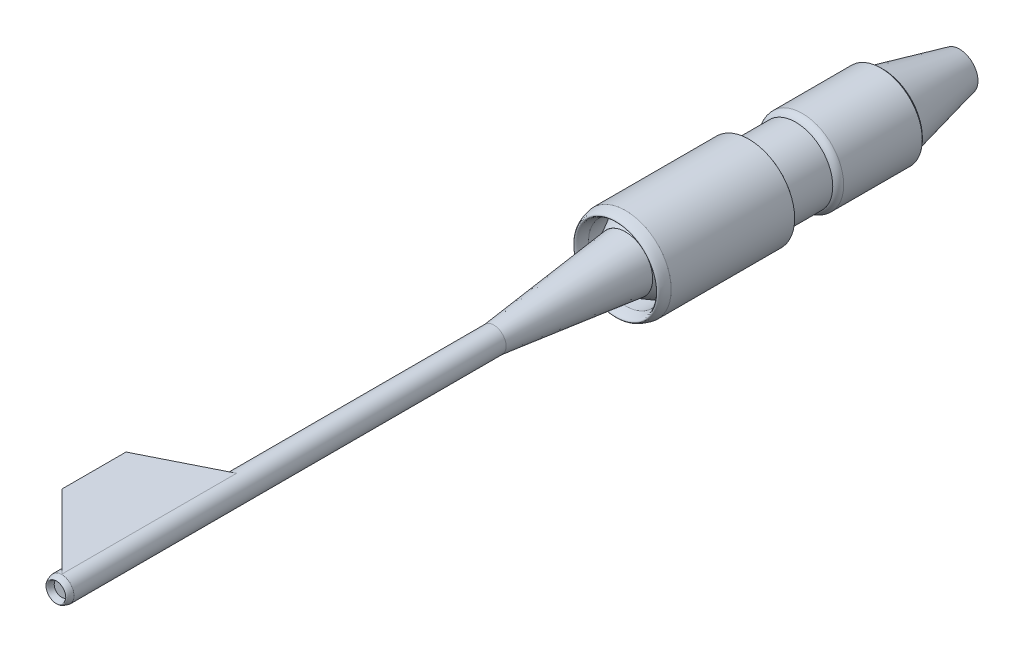
SolidWorks part; units mm, degrees
ref_plane "Front Plane" through (0, 0, 0) normal (0, 0, 1) x (1, 0, 0)
ref_plane "Top Plane" through (0, 0, 0) normal (0, 1, 0) x (1, 0, 0)
ref_plane "Right Plane" through (0, 0, 0) normal (1, 0, 0) x (0, 0, -1)
sketch "Sketch1" plane through (0, 0, 0) normal (0, 0, 1) x (1, 0, 0)
  circle A0 centre (0, 0) radius 416.25
  circle A1 centre (0, 0) radius 337.5
extrude "Boss-Extrude1" add sketch "Sketch1" against normal blind 1125
sketch "Sketch2" plane through (0, 0, 0) normal (1, 0, 0) x (0, 0, -1)
  line L0 (0, 416.25) -> (0, 337.5) construction
  line L1 (0, 337.5) -> (0, 376.875) construction
  line L2 (0, 376.875) -> (-90, 376.875) construction
  line L3 (0, 416.25) -> (0, 337.5)
  line L4 (0, 0) -> (98.8797, 0) construction
  spline S0 degree 2 poles (0, 337.5) (-180, 376.875) (0, 416.25) knots 0 0 0 1 1 1
revolve "Revolve1" add sketch "Sketch2" angle 360 about L4
ref_plane "Plane1" through (0, 0, 0) normal (0, 0, 1) x (1, 0, 0)
sketch "Sketch3" plane through (0, 0, 0) normal (0, 0, 1) x (1, 0, 0)
  circle A0 centre (0, 0) radius 247.5
sketch "Sketch4" plane through (0, 0, 0) normal (0, 1, 0) x (1, 0, 0)
  line L0 (0, 0) -> (0, -1200)
  line L1 (0, -1200) -> (112.5, -1200)
  line L2 (0, 0) -> (247.5, 0)
  line L3 (-247.5, 0) -> (247.5, 0) construction
  line L4 (-457.875, 0) -> (457.875, 0) construction
  line L5 (247.5, 0) -> (112.5, -1200)
revolve "Revolve2" add sketch "Sketch4" angle 360 about L0
sketch "Sketch5" plane through (0, 0, 1200) normal (0, 0, 1) x (1, 0, 0)
  circle A0 centre (0, 0) radius 112.5
extrude "Boss-Extrude2" add sketch "Sketch5" along normal blind 3937.5
sketch "Sketch14" plane through (0, 0, 0) normal (1, 0, 0) x (0, 0, -1)
  line L0 (-5137.5, 112.5) -> (-5137.5, 67.5)
  line L1 (-5137.5, 112.5) -> (-5137.5, -112.5) construction
  line L2 (-5137.5, 67.5) -> (-5137.5, 90)
  line L3 (-5137.5, 90) -> (-5187.5, 90) construction
  line L4 (-5137.5, 0) -> (-5198.2274, 0) construction
  line L5 (-5137.5, 112.5) -> (-5137.5, -112.5) construction
  spline S0 degree 2 poles (-5137.5, 67.5) (-5237.5, 90) (-5137.5, 112.5) knots 0 0 0 1 1 1
  dimension "D1" = 50
  dimension "D2" = 67.5
  dimension "D3" = 90
revolve "Revolve4" add sketch "Sketch14" angle 360 about L4 region at (0, 90, 5157.5)
sketch "Sketch15" plane through (0, 0, -1125) normal (0, 0, -1) x (-1, 0, 0)
  circle A0 centre (0, 0) radius 337.5
extrude "Boss-Extrude5" add sketch "Sketch15" along normal blind 486 separate body
sketch "Sketch16" plane through (0, 0, -1611) normal (0, 0, -1) x (-1, 0, 0)
  line L0 (0, 337.5) -> (0, 416.25) construction
  line L1 (0, 376.875) -> (79.8334, 376.875) construction
  circle A0 centre (0, 0) radius 337.5 construction
  circle A1 centre (0, 0) radius 337.5 construction
  circle A2 centre (0, 0) radius 416.25 construction
  circle A4 centre (0, 0) radius 376.875
extrude "Boss-Extrude6" add sketch "Sketch16" along normal blind 716
sketch "Sketch17" plane through (0, 0, 0) normal (1, 0, 0) x (0, 0, -1)
  line L0 (2327, 0) -> (3043, 0)
  line L1 (2327, -376.875) -> (2327, 376.875) construction
  line L2 (3043, 0) -> (3043, 168.75)
  line L3 (1611, 337.5) -> (2327, 337.5) construction
  line L4 (2327, 0) -> (2327, 337.5)
  line L5 (2327, 337.5) -> (3043, 168.75)
revolve "Revolve5" add sketch "Sketch17" angle 360 about L0
sketch "Sketch18" plane through (0, 0, 0) normal (1, 0, 0) x (0, 0, -1)
  line L0 (0, 247.5) -> (306.6324, 416.25)
  line L1 (1125, 416.25) -> (0, 416.25) construction
  line L2 (0, 247.5) -> (306.6324, 247.5)
  line L3 (306.6324, 247.5) -> (306.6324, 416.25)
  line L4 (0, 0) -> (306.6324, 0) construction
revolve "Revolve6" add sketch "Sketch18" angle 360 about L4
sketch "Sketch19" plane through (0, 0, 0) normal (1, 0, 0) x (0, 0, -1)
  line L1 (1611, 337.5) -> (1611, -337.5) construction
  line L2 (1611, 0) -> (1611, 337.5) construction
  line L3 (1611, 337.5) -> (1551, 337.5)
  line L4 (1611, 0) -> (1571, 0) construction
  line L5 (1611, 337.5) -> (1125, 337.5) construction
  line L6 (1611, 337.5) -> (1611, 376.875)
  line L7 (1611, 376.875) -> (1611, -376.875) construction
  arc A0 (1551, 337.5) -> (1611, 376.875) centre (1614.9642, 305.4325) cw
revolve "Revolve9" add sketch "Sketch19" angle 360 about L4
sketch "Sketch20" plane through (0, 0, 0) normal (1, 0, 0) x (0, 0, -1)
  line L0 (1125, 337.5) -> (1125, 416.25)
  line L1 (1125, 337.5) -> (1155, 337.5)
  line L2 (1551, 337.5) -> (1125, 337.5) construction
  line L3 (1125, 0) -> (1175, 0) construction
  line L4 (1125, -416.25) -> (1125, 416.25) construction
  conic Q0 (1155, 337.5) -> (1125, 416.25) control (1155, 382.5893) rho 0.44632
revolve "Revolve11" add sketch "Sketch20" angle 360 about L3
sketch "Sketch21" plane through (0, 0, 0) normal (1, 0, 0) x (0, 0, -1)
  line L0 (2327, 337.5) -> (2327, 376.875)
  line L1 (2327, 0) -> (2377, 0) construction
  line L2 (2327, -376.875) -> (2327, 376.875) construction
  line L3 (2327, 337.5) -> (2356.2, 330.618)
  line L4 (3043, 168.75) -> (2327, 337.5) construction
  conic Q0 (2327, 376.875) -> (2356.2, 330.618) control (2356.2, 357.1875) rho 0.453502
revolve "Revolve12" add sketch "Sketch21" angle 360 about L1
sketch3d "3DSketch1"
  line L0 (1.7689, 112.4861, 5137.5) -> (-673.2311, 112.4861, 5137.5) construction
  circle A0 centre (0, 0, 5137.5) radius 112.5 construction
  point P2 (0, 0, 5250)
ref_plane "Plane2" through (0, 112.4861, 0) normal (0, 1, 0) x (1, 0, 0)
sketch "Sketch22" plane through (0, 112.4861, 0) normal (0, 1, 0) x (1, 0, 0)
  line L0 (1.7689, -5137.5) -> (1.7689, -3540)
  line L1 (-673.2311, -5137.5) -> (-673.2311, -4462.5) construction
  line L2 (-673.2311, -4462.5) -> (1.7689, -4462.5) construction
  line L3 (-673.2311, -4462.5) -> (1.7689, -5137.5)
  line L4 (-673.2311, -4462.5) -> (-673.2311, -3877.5)
  line L5 (-673.2311, -3877.5) -> (1.7689, -3540)
extrude "Boss-Extrude7" add sketch "Sketch22" against normal blind 50
sketch3d "3DSketch3"
  line L0 (0, 0, 0) -> (416.25, 0, 0)
  line L1 (416.25, 0, 0) -> (416.25, 0, -1125)
  line L2 (0, 0, 0) -> (409.9262, -72.2811, 0)
  line L3 (409.9262, -72.2811, 0) -> (416.438, -35.3508, 0)
  line L4 (409.9262, -72.2811, 0) -> (403.4144, -109.2113, 0)
  line L5 (0, 0, 0) -> (-416.25, 0, 0)
  line L6 (-416.25, 0, 0) -> (-416.25, -37.5, 0)
  line L7 (-416.25, 0, 0) -> (-416.25, 37.5, 0)
  circle A0 centre (0, 0, 0) radius 416.25 construction
  arc A1 (416.25, 0, 0) -> (409.9262, -72.2811, 0) centre (0, 0, 0) cw
  circle A2 centre (0, 0, -1125) radius 416.25 construction
  point P5 (0, 0, 416.25)
  point P9 (0, 0, -708.75)
  point P11 (0, 0, -416.25)
  dimension "D1" = 180
  dimension "D2" = 90
